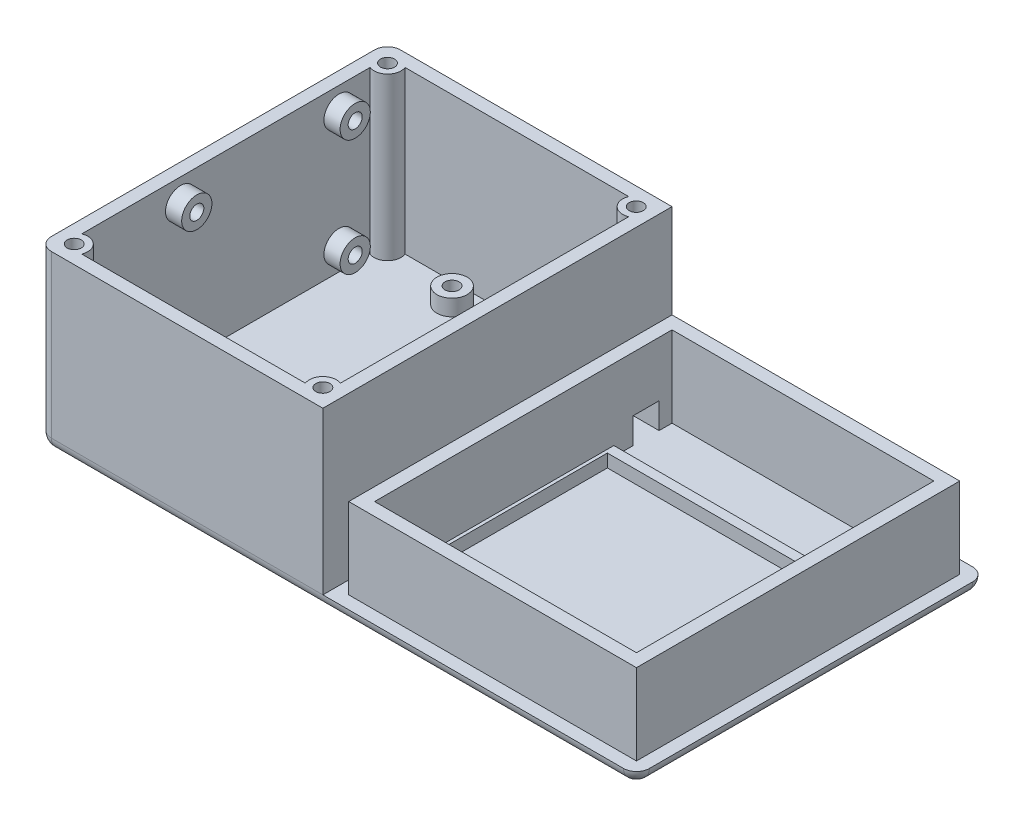
SolidWorks part; units mm, degrees
ref_plane "Front Plane" through (0, 0, 0) normal (0, 0, 1) x (1, 0, 0)
ref_plane "Top Plane" through (0, 0, 0) normal (0, 1, 0) x (1, 0, 0)
ref_plane "Right Plane" through (0, 0, 0) normal (1, 0, 0) x (0, 0, -1)
sketch "Sketch1" plane through (0, 0, 0) normal (0, 1, 0) x (1, 0, 0)
  line L1 (-88.5, -54) -> (88.5, -54)
  line L2 (-92.5, -50) -> (-92.5, 50)
  line L3 (-88.5, 54) -> (88.5, 54)
  line L4 (92.5, -50) -> (92.5, 50)
  line L5 (-92.5, -54) -> (92.5, 54) construction
  line L6 (-92.5, 54) -> (92.5, -54) construction
  arc A0 (-88.5, -54) -> (-92.5, -50) centre (-88.5, -50) cw
  arc A1 (88.5, -54) -> (92.5, -50) centre (88.5, -50) ccw
  arc A2 (88.5, 54) -> (92.5, 50) centre (88.5, 50) cw
  arc A3 (-92.5, 50) -> (-88.5, 54) centre (-88.5, 50) cw
  point P0 (0, 0)
  dimension "D1" = 4
  dimension "D2" = 185
  dimension "D3" = 100
extrude "Boss-Extrude1" add sketch "Sketch1" along normal blind 4
fillet "Fillet1" radius 4 8 edges at (0, 0, 54) (91.3284, 0, 52.8284) (92.5, 0, 0) (91.3284, 0, -52.8284) (0, 0, -54) (-91.3284, 0, -52.8284) (-92.5, 0, 0) (-91.3284, 0, 52.8284)
sketch "Sketch4" plane through (0, 4, 0) normal (0, 1, 0) x (1, 0, 0)
  line L0 (-88.5, -54) -> (88.5, -54) construction
  line L1 (92.5, -50) -> (92.5, 50) construction
  line L2 (88.5, 54) -> (-88.5, 54) construction
  line L3 (-92.5, 50) -> (-92.5, -50) construction
  line L4 (-88.5, -54) -> (88.5, -54)
  line L5 (92.5, -50) -> (92.5, 50)
  line L6 (88.5, 54) -> (-88.5, 54)
  line L7 (-92.5, 50) -> (-92.5, -50)
  line L8 (-88.5, -50) -> (88.5, -50)
  line L9 (88.5, -50) -> (88.5, 50)
  line L10 (88.5, 50) -> (-88.5, 50)
  line L11 (-88.5, 50) -> (-88.5, -50)
  line L12 (3.5, 46) -> (84.5, 46)
  line L13 (3.5, 54) -> (-0.5, 54)
  line L14 (3.5, 54) -> (3.5, -54)
  line L15 (3.5, -54) -> (-0.5, -54)
  line L16 (-0.5, 54) -> (-0.5, -54)
  line L17 (-4.5, 54) -> (-8.5, 54)
  line L18 (-4.5, 54) -> (-4.5, -54)
  line L19 (-4.5, -54) -> (-8.5, -54)
  line L20 (-8.5, 54) -> (-8.5, -54)
  line L21 (84.5, 46) -> (84.5, -46)
  line L22 (84.5, -46) -> (3.5, -46)
  arc A0 (-88.5, 54) -> (-92.5, 50) centre (-88.5, 50) ccw construction
  arc A1 (-92.5, -50) -> (-88.5, -54) centre (-88.5, -50) ccw construction
  arc A2 (88.5, -54) -> (92.5, -50) centre (88.5, -50) ccw construction
  arc A3 (92.5, 50) -> (88.5, 54) centre (88.5, 50) ccw construction
  arc A4 (-92.5, -50) -> (-88.5, -54) centre (-88.5, -50) ccw
  arc A5 (88.5, -54) -> (92.5, -50) centre (88.5, -50) ccw
  arc A6 (92.5, 50) -> (88.5, 54) centre (88.5, 50) ccw
  arc A7 (-88.5, 54) -> (-92.5, 50) centre (-88.5, 50) ccw
  arc A8 (88.5, -50) -> (88.5, -50) centre (88.5, -50) ccw
  arc A9 (88.5, 50) -> (88.5, 50) centre (88.5, 50) ccw
  arc A10 (-88.5, 50) -> (-88.5, 50) centre (-88.5, 50) ccw
  arc A11 (-88.5, -50) -> (-88.5, -50) centre (-88.5, -50) ccw
  arc M17 (-92.5, -50) -> (-88.5, -54) centre (-88.5, -50) ccw
  line M18 (-88.5, -54) -> (88.5, -54)
  line M22 (88.5, 54) -> (-88.5, 54)
  arc M23 (-88.5, 54) -> (-92.5, 50) centre (-88.5, 50) ccw
  line M24 (-92.5, 50) -> (-92.5, -50)
  dimension "D2" = 4
  dimension "D3" = 4
  dimension "D4" = 4
  dimension "D5" = 85
  dimension "D6" = 4
  dimension "D7" = 4
  dimension "D8" = 4
  dimension "D1" = 4
extrude "Boss-Extrude2" add sketch "Sketch4" along normal blind 50 contours L20 L8 L11 L10 M22 M23 M24 M17 M18 | L6 L20 L10 L18 | L10 L20 L8 L18 | L8 L20 L4 L18 region at (-90.361, 4, 51.861) region at (-6.5, 4, 52) region at (-6.5, 4, 0) region at (-6.5, 4, -52)
extrude "Boss-Extrude3" add sketch "Sketch4<3>" along normal blind 25 contours L10 L16 L8 L14 | L21 L22 L14 L8 L9 L10 L12 region at (1.5, 4, 0) region at (4.8124, 4, 48)
sketch "Sketch4<3>" plane through (0, 4, 0) normal (0, 1, 0) x (1, 0, 0) same geometry as "Sketch4"
sketch "Sketch5" plane through (-8.5, 0, 0) normal (-1, 0, 0) x (0, 0, 1)
  line L0 (-50, 4) -> (50, 4) construction
  line L1 (-42, 4) -> (-34, 4)
  line L2 (-42, 4) -> (-42, 12)
  line L3 (-42, 12) -> (-34, 12)
  line L4 (-34, 4) -> (-34, 12)
  line L6 (-46, 4) -> (-30, 4)
  line L7 (-46, 4) -> (-46, 16)
  line L8 (-46, 16) -> (-30, 16)
  line L9 (-30, 4) -> (-30, 16)
  line L10 (-50, 54) -> (-50, 4) construction
  point P6 (-38, 12)
  point P12 (-38, 16)
  line M5 (-50, 4) -> (50, 4)
  dimension "D1" = 8
  dimension "D2" = 4
  dimension "D3" = 4
  dimension "D4" = 4
extrude "Boss-Extrude4" add sketch "Sketch5" against normal up to surface (12 mm away) contours L9 L8 L7 L2 L3 L4 M5 region at (-8.5, 4.2, -44) up to face at (3.5, 16.5, 0)
extrude "Cut-Extrude1" cut sketch "Sketch5<3>" against normal up to surface (12 mm away) contours L4 L3 L2 M5 region at (-8.5, 8, -38) up to face at (3.5, 16.5, 0)
sketch "Sketch5<3>" plane through (-8.5, 0, 0) normal (-1, 0, 0) x (0, 0, 1) same geometry as "Sketch5"
sketch "Sketch6" plane through (0, 4, 0) normal (0, 1, 0) x (1, 0, 0)
  line L0 (5, 24.5) -> (83, 24.5) construction
  line L1 (4.5, 25) -> (83.5, 25)
  line L2 (4.5, 25) -> (4.5, -25)
  line L3 (4.5, -25) -> (83.5, -25)
  line L4 (83.5, 25) -> (83.5, -25)
  line L5 (5, -24.5) -> (5, 24.5) construction
  line L6 (88.5, -50) -> (88.5, 50) construction
  line L7 (88.5, 28) -> (3.5, 28)
  line L8 (88.5, 28) -> (88.5, -28)
  line L9 (88.5, -28) -> (3.5, -28)
  line L10 (3.5, 28) -> (3.5, -28)
  line L11 (3.5, 34) -> (3.5, -46) construction
  point P8 (5, 0)
  point P9 (4.5, 0)
  point P10 (44, 24.5)
  point P11 (44, 25)
  point P20 (3.5, 0)
  line M15 (3.5, 34) -> (3.5, -46)
  dimension "D1" = 0.5
  dimension "D2" = 0.5
  dimension "D3" = 3
extrude "Cut-Extrude2" cut sketch "Sketch6" against normal blind 1 contours L4 L1 L2 L3 region at (44, 4, 0)
extrude "Boss-Extrude5" add sketch "Sketch6<3>" along normal blind 3 contours L9 L7 L1 L4 L3 L2 M15 region at (87.4821, 4, 0)
sketch "Sketch6<3>" plane through (0, 4, 0) normal (0, 1, 0) x (1, 0, 0) same geometry as "Sketch6"
sketch "Sketch7" plane through (0, 4, 0) normal (0, 1, 0) x (1, 0, 0)
  line L2 (-88.5, 50) -> (-86.962, 48.462) construction
  line L3 (-8.5, 50) -> (-88.5, 50) construction
  line L4 (-4.5, 0) -> (-92.5, 0) construction
  line L5 (-4.5, 54) -> (-4.5, -54) construction
  line L6 (-92.5, 50) -> (-92.5, -50) construction
  line L7 (-48.5, -54) -> (-48.5, 54) construction
  line L8 (-88.5, -54) -> (-4.5, -54) construction
  line L9 (-4.5, 54) -> (-88.5, 54) construction
  line L10 (-8.5, 50) -> (-10.038, 48.462) construction
  line L11 (-8.5, -50) -> (-10.038, -48.462) construction
  line L12 (-88.5, -50) -> (-86.962, -48.462) construction
  circle A0 centre (-86.962, 48.462) radius 2.175
  circle A1 centre (-86.962, 48.462) radius 4.175
  circle A2 centre (-10.038, 48.462) radius 4.175
  circle A3 centre (-10.038, 48.462) radius 2.175
  circle A4 centre (-10.038, -48.462) radius 2.175
  circle A5 centre (-10.038, -48.462) radius 4.175
  circle A6 centre (-86.962, -48.462) radius 4.175
  circle A7 centre (-86.962, -48.462) radius 2.175
  point P21 (-48.5, 0)
  dimension "D1" = 4.35
  dimension "D2" = 2
  dimension "D3" = 45
extrude "Boss-Extrude6" add sketch "Sketch7" along normal up to surface (50 mm away) contours A1 | A2 | A6 | A5 up to face at (-48.5, 54, 0)
extrude "Cut-Extrude3" cut sketch "Sketch7<2>" against normal blind 5 from surface contours A0 | A3 | A4 | A7 starting at face at (-48.5, 54, 0)
sketch "Sketch7<2>" plane through (0, 4, 0) normal (0, 1, 0) x (1, 0, 0) same geometry as "Sketch7"
sketch "Sketch9" plane through (0, 4, 0) normal (0, 1, 0) x (1, 0, 0)
  line L0 (-13.9194, 50) -> (-83.0806, 50) construction
  line L2 (-8.5, 44.5806) -> (-8.5, -44.5806) construction
  circle A0 centre (-62.3, 43.75) radius 2.175
  circle A1 centre (-20.3, 43.75) radius 2.175
  circle A2 centre (-62.3, -16.25) radius 2.175
  circle A3 centre (-20.3, -16.25) radius 2.175
  circle A4 centre (-62.3, 43.75) radius 4.675
  circle A5 centre (-20.3, 43.75) radius 4.675
  circle A6 centre (-62.3, -16.25) radius 4.675
  circle A7 centre (-20.3, -16.25) radius 4.675
  dimension "D1" = 4.35
  dimension "D3" = 11.8
  dimension "D4" = 42
  dimension "D5" = 60
  dimension "D6" = 2.5
  dimension "D2" = 6.25
extrude "Boss-Extrude7" add sketch "Sketch9" along normal blind 5
sketch "Sketch10" plane through (-88.5, 0, 0) normal (1, 0, 0) x (0, 0, -1)
  circle A0 centre (-14, 47) radius 2.175
  circle A1 centre (35, 47) radius 2.175
  circle A2 centre (-14, 11) radius 2.175
  circle A3 centre (35, 11) radius 2.175
  circle A4 centre (-14, 47) radius 4.675
  circle A5 centre (35, 47) radius 4.675
  circle A6 centre (35, 11) radius 4.675
  circle A7 centre (-14, 11) radius 4.675
  dimension "D1" = 4.35
  dimension "D2" = 2.5
extrude "Boss-Extrude8" add sketch "Sketch10" along normal blind 5
equation "\"D3@Sketch4\"=\"D2@Sketch4\""
